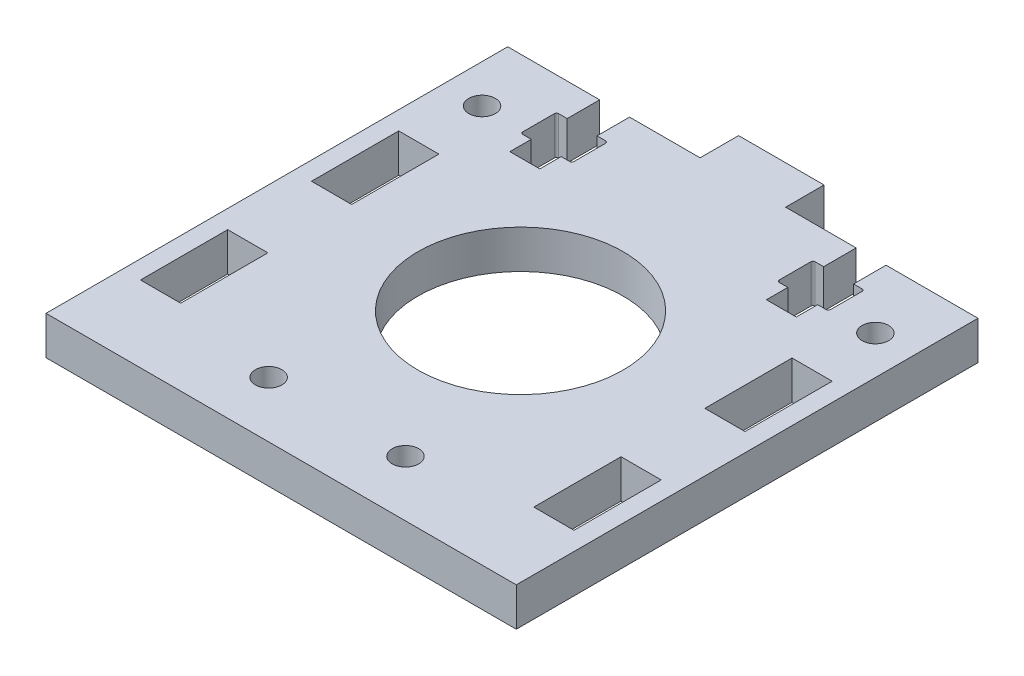
SolidWorks part; units mm, degrees
ref_plane "Front Plane" through (0, 0, 0) normal (0, 0, 1) x (1, 0, 0)
ref_plane "Top Plane" through (0, 0, 0) normal (0, 1, 0) x (1, 0, 0)
ref_plane "Right Plane" through (0, 0, 0) normal (1, 0, 0) x (0, 0, -1)
sketch "Sketch1" plane through (0, 0, 0) normal (0, 1, 0) x (1, 0, 0)
  line L1 (-27.5, 27) -> (27.5, 27)
  line L2 (-27.5, 27) -> (-27.5, -27)
  line L3 (-27.5, -27) -> (27.5, -27)
  line L4 (27.5, 27) -> (27.5, -27)
  line L5 (-27.5, 27) -> (27.5, -27) construction
  line L6 (-27.5, -27) -> (27.5, 27) construction
  point P0 (0, 0)
  dimension "D1" = 55
  dimension "D2" = 54
extrude "MainShape" add sketch "Sketch1" along normal blind 4.5
sketch "Sketch2" plane through (0, 4.5, 0) normal (0, 1, 0) x (1, 0, 0)
  line L0 (0, -27) -> (0, 27) construction
  line L1 (-27.5, -27) -> (27.5, -27) construction
  line L2 (27.5, 27) -> (-27.5, 27) construction
  line L4 (-5, 31.5) -> (5, 31.5)
  line L5 (-5, 31.5) -> (-5, 22.5)
  line L6 (-5, 22.5) -> (5, 22.5)
  line L7 (5, 31.5) -> (5, 22.5)
  line L8 (-5, 31.5) -> (5, 22.5) construction
  line L9 (-5, 22.5) -> (5, 31.5) construction
  dimension "D2" = 4.5
extrude "Tab1" add sketch "Sketch2" against normal through all
sketch "Sketch4" plane through (0, 4.5, 0) normal (0, 1, 0) x (1, 0, 0)
  line L0 (0, 31.5) -> (0, -27) construction
  line L1 (5, 31.5) -> (-5, 31.5) construction
  line L2 (-27.5, -27) -> (27.5, -27) construction
  line L3 (-15, 27) -> (-15, 16.5) construction
  line L4 (-5, 27) -> (-27.5, 27) construction
  line L5 (-13.25, 16.5) -> (-16.75, 16.5) construction
  line L6 (-16.75, 16.5) -> (-16.75, 27) construction
  line L7 (-13.25, 16.5) -> (-16.75, 16.5)
  line L8 (-16.75, 16.5) -> (-16.75, 19)
  line L9 (-16.75, 19) -> (-17.75, 19)
  line L10 (-18, 19.25) -> (-18, 22.95)
  line L11 (-17.75, 23.2) -> (-16.75, 23.2)
  line L12 (-16.75, 23.2) -> (-16.75, 27)
  line L13 (-16.75, 27) -> (-13.25, 27)
  line L14 (-13.25, 16.5) -> (-13.25, 27) construction
  line L15 (-13.25, 23.2) -> (-13.25, 27)
  line L16 (-12.25, 23.2) -> (-13.25, 23.2)
  line L17 (-12, 19.25) -> (-12, 22.95)
  line L18 (-13.25, 19) -> (-12.25, 19)
  line L19 (-13.25, 16.5) -> (-13.25, 19)
  line L20 (13.25, 16.5) -> (13.25, 27) construction
  line L21 (16.75, 16.5) -> (16.75, 27) construction
  line L22 (13.25, 16.5) -> (16.75, 16.5) construction
  line L23 (15, 27) -> (15, 16.5) construction
  line L24 (13.25, 16.5) -> (13.25, 19)
  line L25 (13.25, 19) -> (12.25, 19)
  line L26 (12, 19.25) -> (12, 22.95)
  line L27 (12.25, 23.2) -> (13.25, 23.2)
  line L28 (13.25, 23.2) -> (13.25, 27)
  line L29 (16.75, 27) -> (13.25, 27)
  line L30 (16.75, 23.2) -> (16.75, 27)
  line L31 (17.75, 23.2) -> (16.75, 23.2)
  line L32 (18, 19.25) -> (18, 22.95)
  line L33 (16.75, 19) -> (17.75, 19)
  line L34 (16.75, 16.5) -> (16.75, 19)
  line L35 (13.25, 16.5) -> (16.75, 16.5)
  arc A0 (-17.75, 19) -> (-18, 19.25) centre (-17.75, 19.25) cw
  arc A1 (-12, 19.25) -> (-12.25, 19) centre (-12.25, 19.25) cw
  arc A2 (-12.25, 23.2) -> (-12, 22.95) centre (-12.25, 22.95) cw
  arc A3 (-18, 22.95) -> (-17.75, 23.2) centre (-17.75, 22.95) cw
  arc A4 (18, 22.95) -> (17.75, 23.2) centre (17.75, 22.95) ccw
  arc A5 (12.25, 23.2) -> (12, 22.95) centre (12.25, 22.95) ccw
  arc A6 (12, 19.25) -> (12.25, 19) centre (12.25, 19.25) ccw
  arc A7 (17.75, 19) -> (18, 19.25) centre (17.75, 19.25) ccw
  point P24 (-18, 19)
  point P27 (-12, 19)
  point P30 (-12, 23.2)
  point P33 (-18, 23.2)
  point P56 (18, 23.2)
  point P57 (12, 23.2)
  point P58 (12, 19)
  point P59 (18, 19)
  dimension "D7" = 0.25
  dimension "D1" = 10.5
  dimension "D2" = 1.75
  dimension "D3" = 4.2
  dimension "D4" = 3
  dimension "D5" = 8
  dimension "D6" = 15
extrude "Cut-Extrude2" cut sketch "Sketch4" against normal through all
sketch "Sketch5" plane through (0, 4.5, 0) normal (0, 1, 0) x (1, 0, 0)
  line L0 (0, -27) -> (0, 31.5) construction
  line L1 (-27.5, -27) -> (27.5, -27) construction
  line L2 (5, 31.5) -> (-5, 31.5) construction
  line L3 (23, 27) -> (23, -27) construction
  line L4 (27.5, 27) -> (16.75, 27) construction
  line L5 (-23, 27) -> (-23, -27) construction
  line L6 (20.65, 12.1) -> (25.35, 12.1)
  line L7 (20.65, 12.1) -> (20.65, 1.9)
  line L8 (20.65, 1.9) -> (25.35, 1.9)
  line L9 (25.35, 12.1) -> (25.35, 1.9)
  line L10 (20.65, 12.1) -> (25.35, 1.9) construction
  line L11 (20.65, 1.9) -> (25.35, 12.1) construction
  line L12 (-20.65, 1.9) -> (-25.35, 12.1) construction
  line L13 (-20.65, 12.1) -> (-25.35, 1.9) construction
  line L14 (-25.35, 12.1) -> (-25.35, 1.9)
  line L15 (-20.65, 1.9) -> (-25.35, 1.9)
  line L16 (-20.65, 12.1) -> (-20.65, 1.9)
  line L17 (-20.65, 12.1) -> (-25.35, 12.1)
  line L18 (-27.5, -3) -> (27.5, -3) construction
  line L19 (-27.5, 27) -> (-27.5, -27) construction
  line L20 (27.5, -27) -> (27.5, 27) construction
  line L21 (-20.65, -18.1) -> (-25.35, -7.9) construction
  line L22 (-20.65, -7.9) -> (-25.35, -18.1) construction
  line L23 (20.65, -7.9) -> (25.35, -18.1) construction
  line L24 (20.65, -18.1) -> (25.35, -7.9) construction
  line L25 (-20.65, -18.1) -> (-25.35, -18.1)
  line L26 (-20.65, -18.1) -> (-20.65, -7.9)
  line L27 (-20.65, -7.9) -> (-25.35, -7.9)
  line L28 (-25.35, -18.1) -> (-25.35, -7.9)
  line L29 (25.35, -18.1) -> (25.35, -7.9)
  line L30 (20.65, -7.9) -> (25.35, -7.9)
  line L31 (20.65, -18.1) -> (20.65, -7.9)
  line L32 (20.65, -18.1) -> (25.35, -18.1)
  line L33 (-20.65, 12.1) -> (-25.35, 1.9) construction
  point P10 (23, 7)
  point P21 (-23, 7)
  point P36 (-23, -13)
  point P37 (23, -13)
  dimension "D1" = 23
  dimension "D2" = 10.2
  dimension "D3" = 4.7
  dimension "D4" = 20
  dimension "D5" = 20
extrude "Cut-Extrude3" cut sketch "Sketch5" against normal through all
sketch "Sketch6" plane through (0, 4.5, 0) normal (0, 1, 0) x (1, 0, 0)
  line L0 (0, -27) -> (0, 27) construction
  line L1 (5, 31.5) -> (-5, 31.5) construction
  line L3 (-27.5, 1) -> (27.5, 1) construction
  line L4 (-27.5, 27) -> (-27.5, -27) construction
  line L5 (27.5, -27) -> (27.5, 27) construction
  line L6 (27.5, 27) -> (16.75, 27) construction
  line L7 (-27.5, -27) -> (27.5, -27) construction
  line L9 (-27.5, 27) -> (27.5, 27) construction
  circle A0 centre (0, 1) radius 12
  point P4 (0, 31.5)
  dimension "D1" = 24
  dimension "D2" = 26
extrude "Cut-Extrude4" cut sketch "Sketch6" against normal through all
sketch "Sketch7" plane through (0, 4.5, 0) normal (0, 1, 0) x (1, 0, 0)
  line L0 (0, 1) -> (0, -27) construction
  line L3 (-27.5, -27) -> (27.5, -27) construction
  line L4 (8, -20.46) -> (-8, -20.46) construction
  circle A1 centre (-8, -20.46) radius 1.55
  circle A2 centre (8, -20.46) radius 1.55
  point P8 (0, -20.46)
  dimension "D1" = 3.1
  dimension "D3" = 21.46
extrude "Cut-Extrude5" [suppressed] cut sketch "Sketch7" against normal through all
sketch "Sketch8" plane through (0, 4.5, 0) normal (0, 1, 0) x (1, 0, 0)
  line L0 (-12, 1) -> (12, 1) construction
  line L1 (0, 1) -> (0, -20.46) construction
  line L2 (8, -20.46) -> (-8, -20.46) construction
  line L3 (0, -11) -> (0, 13) construction
  circle A0 centre (-8, -20.46) radius 1.55
  circle A1 centre (0, 1) radius 12 construction
  circle A2 centre (8, -20.46) radius 1.55
  dimension "D3" = 3.1
  dimension "D1" = 90
  dimension "D4" = 21.46
extrude "Cut-Extrude6" cut sketch "Sketch8" against normal through all
sketch "Sketch9" plane through (0, 4.5, 0) normal (0, 1, 0) x (1, 0, 0)
  line L0 (0, -27) -> (0, 31.5) construction
  line L1 (-27.5, -27) -> (27.5, -27) construction
  line L2 (5, 31.5) -> (-5, 31.5) construction
  line L3 (16, -27) -> (16, -16.5) construction
  line L4 (14.25, -16.5) -> (17.75, -16.5) construction
  line L5 (17.75, -16.5) -> (17.75, -27) construction
  line L6 (17.75, -27) -> (17.75, -23.2)
  line L7 (17.75, -23.2) -> (18.75, -23.2)
  line L8 (19, -22.95) -> (19, -19.25)
  line L9 (18.75, -19) -> (17.75, -19)
  line L10 (17.75, -19) -> (17.75, -16.5)
  line L11 (17.75, -16.5) -> (14.25, -16.5)
  line L12 (17.75, -27) -> (14.25, -27)
  line L13 (14.25, -16.5) -> (14.25, -27) construction
  line L14 (14.25, -19) -> (14.25, -16.5)
  line L15 (13.25, -19) -> (14.25, -19)
  line L16 (13, -22.95) -> (13, -19.25)
  line L17 (14.25, -23.2) -> (13.25, -23.2)
  line L18 (14.25, -27) -> (14.25, -23.2)
  line L19 (-14.25, -16.5) -> (-14.25, -27) construction
  line L20 (-17.75, -16.5) -> (-17.75, -27) construction
  line L21 (-14.25, -16.5) -> (-17.75, -16.5) construction
  line L22 (-16, -27) -> (-16, -16.5) construction
  line L23 (-14.25, -27) -> (-14.25, -23.2)
  line L24 (-14.25, -23.2) -> (-13.25, -23.2)
  line L25 (-13, -22.95) -> (-13, -19.25)
  line L26 (-13.25, -19) -> (-14.25, -19)
  line L27 (-14.25, -19) -> (-14.25, -16.5)
  line L28 (-17.75, -27) -> (-14.25, -27)
  line L29 (-17.75, -16.5) -> (-14.25, -16.5)
  line L30 (-17.75, -19) -> (-17.75, -16.5)
  line L31 (-18.75, -19) -> (-17.75, -19)
  line L32 (-19, -22.95) -> (-19, -19.25)
  line L33 (-17.75, -23.2) -> (-18.75, -23.2)
  line L34 (-17.75, -27) -> (-17.75, -23.2)
  arc A0 (18.75, -23.2) -> (19, -22.95) centre (18.75, -22.95) ccw
  arc A1 (19, -19.25) -> (18.75, -19) centre (18.75, -19.25) ccw
  arc A2 (13, -19.25) -> (13.25, -19) centre (13.25, -19.25) cw
  arc A3 (13.25, -23.2) -> (13, -22.95) centre (13.25, -22.95) cw
  arc A4 (-13.25, -23.2) -> (-13, -22.95) centre (-13.25, -22.95) ccw
  arc A5 (-13, -19.25) -> (-13.25, -19) centre (-13.25, -19.25) ccw
  arc A6 (-19, -19.25) -> (-18.75, -19) centre (-18.75, -19.25) cw
  arc A7 (-18.75, -23.2) -> (-19, -22.95) centre (-18.75, -22.95) cw
  point P16 (19, -23.2)
  point P19 (19, -19)
  point P30 (13, -19)
  point P31 (13, -23.2)
  point P54 (-13, -23.2)
  point P55 (-13, -19)
  point P56 (-19, -19)
  point P57 (-19, -23.2)
  dimension "D7" = 0.25
  dimension "D1" = 10.5
  dimension "D2" = 1.75
  dimension "D3" = 8
  dimension "D4" = 4.2
  dimension "D5" = 3
  dimension "D6" = 16
extrude "Cut-Extrude7" [suppressed] cut sketch "Sketch9" against normal through all
sketch "Sketch10" [suppressed] plane through (0, 0, 27) normal (0, 0, 1) x (1, 0, 0)
  line L0 (-27.5, 2.25) -> (27.5, 2.25) construction
  line L1 (-27.5, 4.5) -> (-27.5, 0) construction
  line L2 (27.5, 4.5) -> (27.5, 0) construction
  line L3 (-16, 4.5) -> (-16, 0) construction
  line L4 (-14.25, 4.5) -> (-17.75, 4.5) construction
  line L5 (16, 4.5) -> (16, 0) construction
  line L6 (17.75, 4.5) -> (14.25, 4.5) construction
  line L7 (17.75, 0) -> (14.25, 0) construction
  line L8 (-14.25, 0) -> (-17.75, 0) construction
  circle A0 centre (-16, 2.25) radius 1.6
  circle A1 centre (16, 2.25) radius 1.6
  dimension "D1" = 3.2
  dimension "D2" = 3.2
sketch "Sketch11" plane through (0, 4.5, 0) normal (0, 1, 0) x (1, 0, 0)
  line L0 (-20.65, 7) -> (-25.35, 7) construction
  line L1 (-20.65, 1.9) -> (-20.65, 12.1) construction
  line L2 (-25.35, 12.1) -> (-25.35, 1.9) construction
  line L3 (-23, 7) -> (-23, 27) construction
  line L4 (-16.75, 27) -> (-27.5, 27) construction
  line L5 (0, 31.5) -> (0, 0) construction
  line L6 (5, 31.5) -> (-5, 31.5) construction
  line L7 (23, 7) -> (23, 27) construction
  line L8 (20.65, 7) -> (25.35, 7) construction
  line L9 (-23, 7) -> (-23, 27) construction
  circle A0 centre (-23, 19.5) radius 1.55
  circle A1 centre (23, 19.5) radius 1.55
  dimension "D1" = 3.1
  dimension "D2" = 7.5
extrude "Cut-Extrude8" cut sketch "Sketch11" against normal through all
sketch "Sketch12" [suppressed] plane through (0, 4.5, 0) normal (0, 1, 0) x (1, 0, 0)
  line L0 (-27.5, -7) -> (-34, -17)
  line L1 (-27.5, 27) -> (-27.5, -27) construction
  line L2 (-34, -17) -> (-34, -27)
  line L3 (-34, -27) -> (-27.5, -27)
  line L4 (-27.5, -27) -> (-27.5, -7)
  line L5 (-27.5, -27) -> (27.5, -27) construction
  line L6 (0, -27) -> (0, 31.5) construction
  line L7 (5, 31.5) -> (-5, 31.5) construction
  line L8 (27.5, -27) -> (27.5, -7)
  line L9 (34, -27) -> (27.5, -27)
  line L10 (34, -17) -> (34, -27)
  line L11 (27.5, -7) -> (34, -17)
  point P4 (0, -27)
  dimension "D1" = 34
  dimension "D2" = 10
  dimension "D3" = 20
extrude "Boss-Extrude1" [suppressed] add sketch "Sketch12" against normal through all
sketch "Sketch14" [suppressed] plane through (0, 4.5, 0) normal (0, 1, 0) x (1, 0, 0)
  line L0 (-34, -27) -> (34, -27) construction
  line L2 (-34, -27) -> (34, -27) construction
  line L3 (0, -27) -> (0, 31.5) construction
  line L4 (5, 31.5) -> (-5, 31.5) construction
  line L6 (26.25, -16.5) -> (26.25, -27) construction
  line L8 (-28, -27) -> (-28, -16.5) construction
  line L9 (-26.25, -16.5) -> (-29.75, -16.5) construction
  line L10 (-29.75, -16.5) -> (-29.75, -27) construction
  line L11 (-26.25, -27) -> (-29.75, -27)
  line L12 (-29.75, -27) -> (-29.75, -23.2)
  line L13 (-29.75, -23.2) -> (-30.75, -23.2)
  line L14 (-31, -22.95) -> (-31, -19.25)
  line L15 (-30.75, -19) -> (-29.75, -19)
  line L16 (-29.75, -19) -> (-29.75, -16.5)
  line L17 (-29.75, -16.5) -> (-26.25, -16.5)
  line L18 (-26.25, -16.5) -> (-26.25, -27) construction
  line L19 (-26.25, -19) -> (-26.25, -16.5)
  line L20 (-25.25, -19) -> (-26.25, -19)
  line L21 (-25, -22.95) -> (-25, -19.25)
  line L22 (-26.25, -23.2) -> (-25.25, -23.2)
  line L23 (-26.25, -27) -> (-26.25, -23.2)
  line L24 (29.75, -16.5) -> (29.75, -27) construction
  line L25 (26.25, -16.5) -> (29.75, -16.5) construction
  line L26 (28, -27) -> (28, -16.5) construction
  line L27 (26.25, -27) -> (26.25, -23.2)
  line L28 (26.25, -23.2) -> (25.25, -23.2)
  line L29 (25, -22.95) -> (25, -19.25)
  line L30 (25.25, -19) -> (26.25, -19)
  line L31 (26.25, -19) -> (26.25, -16.5)
  line L32 (29.75, -16.5) -> (26.25, -16.5)
  line L33 (29.75, -19) -> (29.75, -16.5)
  line L34 (30.75, -19) -> (29.75, -19)
  line L35 (31, -22.95) -> (31, -19.25)
  line L36 (29.75, -23.2) -> (30.75, -23.2)
  line L37 (29.75, -27) -> (29.75, -23.2)
  line L38 (26.25, -27) -> (29.75, -27)
  line L39 (-26.25, -16.5) -> (-26.25, -27) construction
  arc A0 (-30.75, -23.2) -> (-31, -22.95) centre (-30.75, -22.95) cw
  arc A1 (-31, -19.25) -> (-30.75, -19) centre (-30.75, -19.25) cw
  arc A2 (-25, -19.25) -> (-25.25, -19) centre (-25.25, -19.25) ccw
  arc A3 (-25.25, -23.2) -> (-25, -22.95) centre (-25.25, -22.95) ccw
  arc A4 (25.25, -23.2) -> (25, -22.95) centre (25.25, -22.95) cw
  arc A5 (25, -19.25) -> (25.25, -19) centre (25.25, -19.25) cw
  arc A6 (31, -19.25) -> (30.75, -19) centre (30.75, -19.25) ccw
  arc A7 (30.75, -23.2) -> (31, -22.95) centre (30.75, -22.95) ccw
  point P2 (0, -27)
  dimension "D10" = 0.25
  dimension "D4" = 1.75
  dimension "D6" = 10.5
  dimension "D2" = 28
  dimension "D3" = 3
  dimension "D5" = 4.2
  dimension "D7" = 8
extrude "Cut-Extrude9" [suppressed] cut sketch "Sketch14" against normal through all
equation "\"X-ROD-SPACING\"=45"
equation "\"Y-ROD-SPACING\"=75"
equation "\"Z-ROD-SPACING\"=17.5"
equation "\"Y-BED-OFFSET\"=2"
equation "\"Y-BED-ROD-INSET\"=3.5"
equation "\"Y-BED-SCREW-SPACING\"=209"
equation "\"Y-BED-SCREW-CUTOUT-SLOT-HEIGHT\"=2"
equation "\"T-SLOT-NUT-FILLET-RADIUS\"=0.25"
equation "\"T-SLOT-SCREW-SHAFT-RADIUS\"=1.75"
equation "\"T-SLOT-SCREW-SHAFT-CUTOUT-LENGTH\"=10.5"
equation "\"T-SLOT-NUT-DEPTH\"=4.2"
equation "\"T-SLOT-NUT-WIDTH\"=3"
equation "\"T-SLOT-NUT-END-DISTANCE\"=8"
equation "\"ACRYLIC-THICKNESS\"=10"
equation "\"ACRYLIC-THICKNESS2\"=4.5"
equation "\"ACRYLIC-TAB-CUTOUT-SIZE\"=\"ACRYLIC-THICKNESS\"+\"ACRYLIC-TAB-TOLERANCE\"*2"
equation "\"ACRYLIC-TAB-WIDTH\"=\"ACRYLIC-THICKNESS\""
equation "\"ACRYLIC-M3-HOLE\"=3.1"
equation "\"SMOOTHROD-CAP-SCREW-DISTANCE\"=20"
equation "\"FRAME-WIDTH-INNER\"=370"
equation "\"NEMA17-HOLE-SPACING\"=31"
equation "\"NEMA17-CENTRAL-CUTOUT\"=22.5"
equation "\"Z-BRACKET-REACH\"=55"
equation "\"Z-ROD-INSET\"=16"
equation "\"TOP-BRACKET-SPACING\"=40"
equation "\"SMOOTHROD-X-LENGTH\"=350"
equation "\"SMOOTHROD-Y-LENGTH\"=350"
equation "\"SMOOTHROD-Z-LENGTH\"=350"
equation "\"SMOOTHROD-TIGHTENING-HEADROOM\"=.25"
equation "\"LEADSCREW-Z-LENGTH\"=300"
equation "\"SCREW-LENGTH-FRAME\"=\"ACRYLIC-THICKNESS\" + 10"
equation "\"SCREW-LENGTH-MOTOR\"=\"ACRYLIC-THICKNESS\" + 5"
equation "\"SCREW-LENGTH-EXTRUDER\"=28"
equation "\"SCREW-HEAD-RADIUS\"=6"
equation "\"PRINTED-X-SMOOTHROD-DIAMETER\"=8.2"
equation "\"PRINTED-X-SMOOTHROD-CUTOUT\"=10"
equation "\"PRINTED-X-BASE-HEIGHT\"=10"
equation "\"PRINTED-LM8UU-CUTOUT-SIZE\"=15.25"
equation "\"PRINTED-LM8UU-CUTOUT-LENGTH\"=24.5"
equation "\"PRINTED-X-IDLER-HEIGHT\"=16"
equation "\"PSU-MOUNTING-WIDTH\"=95"
equation "\"PSU-MOUNTING-HEIGHT\"=177"
equation "\"Y-BELT-TO-ROD-DISTANCE\"=20"
equation "\"SPOOL-HOLDER-ROD-SPACING\"=150"
equation "\"ACRYLIC-X-CARRIAGE-WIDTH\"=55"
equation "\"ACRYLIC-X-CARRIAGE-HEIGHT\"=75"
equation "\"ACRYLIC-X-CARRIAGE-SCREW-SPACING-X\"=15"
equation "\"ACRYLIC-X-CARRIAGE-SCREW-SPACING-Y\"=33"
equation "\"ACRYLIC-X-CARRIAGE-CENTER-TAB-SPACING\"=14"
equation "\"D1@Sketch1\"=\"ACRYLIC-X-CARRIAGE-WIDTH\""
equation "\"D1@MainShape\" = \"ACRYLIC-THICKNESS2\""
equation "\"D1@Sketch2\"=\"ACRYLIC-TAB-WIDTH\""
equation "\"D2@Sketch2\"=\"ACRYLIC-THICKNESS2\""
equation "\"D1@Sketch4\"=\"T-SLOT-SCREW-SHAFT-CUTOUT-LENGTH\""
equation "\"D2@Sketch4\"=\"T-SLOT-SCREW-SHAFT-RADIUS\""
equation "\"D3@Sketch4\"=\"T-SLOT-NUT-DEPTH\""
equation "\"D4@Sketch4\"=\"T-SLOT-NUT-WIDTH\""
equation "\"D5@Sketch4\"=\"T-SLOT-NUT-END-DISTANCE\""
equation "\"D6@Sketch4\"=\"ACRYLIC-X-CARRIAGE-SCREW-SPACING-X\""
equation "\"D7@Sketch4\"=\"T-SLOT-NUT-FILLET-RADIUS\""
equation "\"ACRYLIC-X-CARRIAGE-EXTRUDER-SHELF-DEPTH\"=\"ACRYLIC-X-CARRIAGE-EXTRUDER-OFFSET\" + 28"
equation "\"D2@Sketch1\"=\"ACRYLIC-X-CARRIAGE-EXTRUDER-SHELF-DEPTH\""
equation "\"ACRYLIC-X-CARRIAGE-LM8UU-CUTOUT-WIDTH\"=24.25"
equation "\"ACRYLIC-X-CARRIAGE-EXTRUDER-BRACE-SPACING\"=23"
equation "\"ACRYLIC-X-CARRIAGE-EXTRUDER-BRACE-TAB-OFFSET\"=20"
equation "\"ACRYLIC-X-CARRIAGE-EXTRUDER-BRACE-HEIGHT\"=35"
equation "\"ACRYLIC-X-CARRIAGE-EXTRUDER-BRACE-SCREW-SPACING\"=22"
equation "\"D1@Sketch5\"=\"ACRYLIC-X-CARRIAGE-EXTRUDER-BRACE-SPACING\""
equation "\"D2@Sketch5\"=\"ACRYLIC-TAB-CUTOUT-SIZE\""
equation "\"D3@Sketch5\"=\"ACRYLIC-THICKNESS2\"+\"ACRYLIC-TAB-TOLERANCE\"*2"
equation "\"D4@Sketch5\"=\"ACRYLIC-X-CARRIAGE-EXTRUDER-BRACE-TAB-OFFSET\""
equation "\"D1@Sketch7\"=\"ACRYLIC-M3-HOLE\""
equation "\"D3@Sketch8\"=\"ACRYLIC-M3-HOLE\""
equation "\"ACRYLIC-X-CARRIAGE-EXTRUDER-ANGLE\"=90"
equation "\"D1@Sketch8\"=\"ACRYLIC-X-CARRIAGE-EXTRUDER-ANGLE\""
equation "\"ACRYLIC-X-CARRIAGE-EXTRUDER-OFFSET\"=26"
equation "\"D2@Sketch6\"=\"ACRYLIC-X-CARRIAGE-EXTRUDER-OFFSET\""
equation "\"D1@Sketch9\"=\"T-SLOT-SCREW-SHAFT-CUTOUT-LENGTH\""
equation "\"D2@Sketch9\"=\"T-SLOT-SCREW-SHAFT-RADIUS\""
equation "\"D3@Sketch9\"=\"T-SLOT-NUT-END-DISTANCE\""
equation "\"D4@Sketch9\"=\"T-SLOT-NUT-DEPTH\""
equation "\"D5@Sketch9\"=\"T-SLOT-NUT-WIDTH\""
equation "\"D7@Sketch9\"=\"T-SLOT-NUT-FILLET-RADIUS\""
equation "\"ACRYLIC-TAB-TOLERANCE\"=.1"
equation "\"D1@Sketch11\"=\"ACRYLIC-M3-HOLE\""
equation "\"D6@Sketch14\"=\"T-SLOT-SCREW-SHAFT-CUTOUT-LENGTH\""
equation "\"D3@Sketch14\"=\"T-SLOT-NUT-WIDTH\""
equation "\"D5@Sketch14\"=\"T-SLOT-NUT-DEPTH\""
equation "\"D4@Sketch14\"=\"T-SLOT-SCREW-SHAFT-RADIUS\""
equation "\"D10@Sketch14\"=\"T-SLOT-NUT-FILLET-RADIUS\""
equation "\"D7@Sketch14\"=\"T-SLOT-NUT-END-DISTANCE\""
